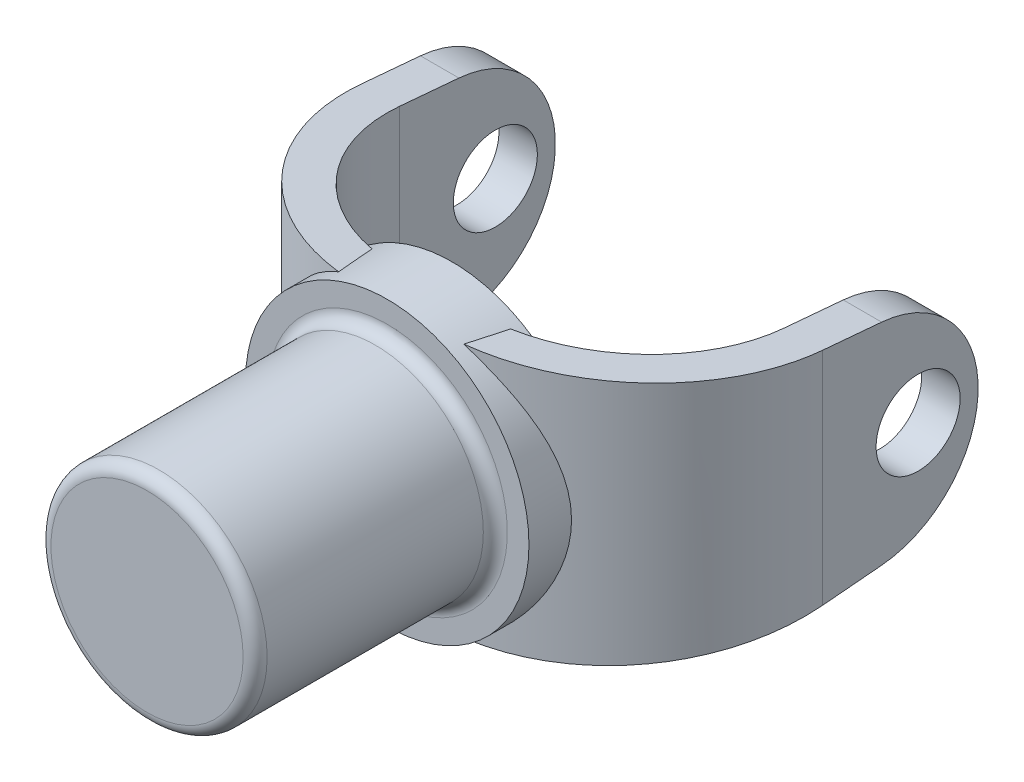
SolidWorks part; units mm, degrees
ref_plane "Front Plane" through (0, 0, 0) normal (0, 0, 1) x (1, 0, 0)
ref_plane "Top Plane" through (0, 0, 0) normal (0, 1, 0) x (1, 0, 0)
ref_plane "Right Plane" through (0, 0, 0) normal (1, 0, 0) x (0, 0, -1)
sketch "Sketch1" plane through (0, 0, 0) normal (0, 0, 1) x (1, 0, 0)
  circle A0 centre (0, 0) radius 225
  dimension "D1" = 450
extrude "Boss-Extrude1" add sketch "Sketch1" against normal blind 500
sketch "Sketch2" plane through (0, 0, -500) normal (0, 0, -1) x (-1, 0, 0)
  circle A0 centre (0, 0) radius 295
  dimension "D1" = 590
extrude "Boss-Extrude2" add sketch "Sketch2" along normal blind 135
fillet "Fillet1" radius 25 2 edges at (225, 0, 0) (225, 0, -500)
sketch "Sketch3" plane through (0, 0, 0) normal (0, 1, 0) x (1, 0, 0)
  line L0 (0, 0) -> (0, 1301.1787) construction
sketch "Sketch5" plane through (0, 0, 0) normal (0, 1, 0) x (1, 0, 0)
  line L0 (0, 525.9365) -> (-80, 525.9365)
  line L1 (0, 0) -> (0, 1301.1787) construction
  line L2 (-480, 925.9365) -> (-480, 1250)
  line L3 (-250, 500) -> (250, 500) construction
  line L4 (0, 605.9365) -> (-80, 605.9365)
  line L5 (-400, 925.9365) -> (-400, 1250)
  line L6 (-480, 1250) -> (-400, 1250)
  line L7 (0, 605.9365) -> (0, 525.9365)
  arc A0 (-80, 525.9365) -> (-480, 925.9365) centre (-80, 925.9365) cw
  arc A1 (-80, 605.9365) -> (-400, 925.9365) centre (-80, 925.9365) cw
  dimension "D2" = 400
  dimension "D1" = 750
  dimension "D3" = 480
  dimension "D4" = 80
extrude "Boss-Extrude3" add sketch "Sketch5" along normal mid plane 548
sketch "Sketch7" plane through (0, 0, 0) normal (1, 0, 0) x (0, 0, -1)
  line L0 (0, 0) -> (1301.1787, 0) construction
  line L1 (500, 295) -> (500, -295) construction
  line L2 (655.4116, 0) -> (1404.5884, 0) construction
  line L3 (500, 250) -> (500, -250) construction
  line L4 (1049.1743, 219.1628) -> (203.0393, 293.19)
  line L5 (1000, 585.309) -> (1000, -585.309) construction
  line L6 (0, 200) -> (0, -200) construction
  line L7 (1049.1743, -219.1628) -> (203.0393, -293.19)
  line L8 (203.0393, 293.19) -> (290.0213, 513.8298)
  line L9 (290.0213, 513.8298) -> (1323.3714, 627.4283)
  line L10 (1323.3714, 627.4283) -> (2049.6065, -712.5949)
  line L11 (2049.6065, -712.5949) -> (1049.1743, -1026.8243)
  line L12 (1049.1743, -1026.8243) -> (203.0393, -293.19)
  circle A0 centre (1125, 0) radius 87.5
  arc A2 (1049.1743, -219.1628) -> (1049.1743, 219.1628) centre (1030, 0) ccw
  point P8 (1250, 0)
  point P12 (1030, 0)
  point P16 (1250, 0)
  point P22 (1000, 0)
  dimension "D2" = 440
  dimension "D3" = 175
  dimension "D5" = 1000
  dimension "D1" = 625
  dimension "D4" = 750
  dimension "D6" = 95
  dimension "D7" = 95
extrude "Cut-Extrude1" cut sketch "Sketch7" against normal blind 548
sketch "Sketch8" plane through (0, 0, -500) normal (0, 0, 1) x (1, 0, 0)
  circle A0 centre (0, 0) radius 295
extrude "Boss-Extrude4" add sketch "Sketch8" against normal up to surface (135 mm away) up to face at (-53.8052, 0, -635)
mirror "Mirror3" about plane through (0, 0, 0) normal (1, 0, 0) of "Boss-Extrude4", "Cut-Extrude1", "Boss-Extrude3"
